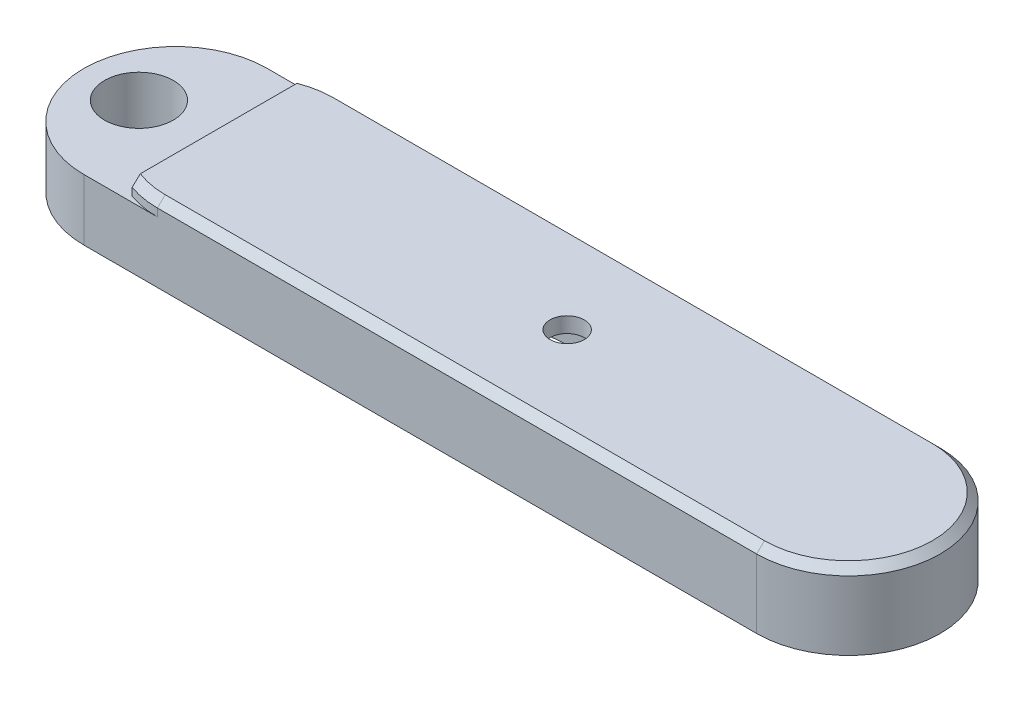
SolidWorks part; units mm, degrees
ref_plane "Front Plane" through (0, 0, 0) normal (0, 0, 1) x (1, 0, 0)
ref_plane "Top Plane" through (0, 0, 0) normal (0, 1, 0) x (1, 0, 0)
ref_plane "Right Plane" through (0, 0, 0) normal (1, 0, 0) x (0, 0, -1)
ref_plane "Plane1" through (0, 14.27, 0) normal (0, 1, 0) x (1, 0, 0)
sketch "Sketch1" plane through (0, 14.27, 0) normal (0, 1, 0) x (1, 0, 0)
  line L0 (8.0333, 3.025) -> (20.0462, 3.9053)
  line L1 (20.0462, 7.8947) -> (8.0333, 8.775)
  line L2 (3.7667, 8.775) -> (-8.2462, 7.8947)
  line L3 (-8.2462, 3.9053) -> (3.7667, 3.025)
  arc A0 (3.7667, 3.025) -> (8.0333, 3.025) centre (5.9, 5.9) ccw
  arc A1 (20.0462, 3.9053) -> (20.0462, 7.8947) centre (19.9, 5.9) ccw
  arc A2 (8.0333, 8.775) -> (3.7667, 8.775) centre (5.9, 5.9) ccw
  arc A3 (-8.2462, 7.8947) -> (-8.2462, 3.9053) centre (-8.1, 5.9) ccw
extrude "Boss-Extrude1" add sketch "Sketch1" against normal blind 1.6
sketch "Sketch2" plane through (0, 12.67, 0) normal (0, -1, 0) x (1, 0, 0)
  circle A0 centre (5.9, -5.9) radius 3.58
extrude "Boss-Extrude2" add sketch "Sketch2" along normal blind 1.83
ref_plane "Plane2" [suppressed] through (0, 0, -5.9) normal (0, 0, 1) x (1, 0, 0)
sketch "Sketch3" [suppressed] plane through (0, 0, -5.9) normal (0, 0, 1) x (1, 0, 0)
  line L0 (8.325, 14.27) -> (5.9, 14.27)
  line L1 (5.9, 14.27) -> (5.9, 10.84)
  line L2 (5.9, 10.84) -> (8.2, 10.84)
  line L3 (8.2, 10.84) -> (8.2, 13.2)
  line L4 (8.2, 13.2) -> (6.75, 13.2)
  line L5 (6.75, 13.2) -> (6.75, 13.65)
  line L6 (6.75, 13.65) -> (8.325, 13.65)
  line L7 (8.325, 13.65) -> (8.325, 14.27)
  line L8 (5.9, 14.27) -> (5.9, 10.84) construction
revolve "Cut-Revolve1" [suppressed] cut sketch "Sketch3" angle 360 about L8 reverse direction yes
hole_wizard "Ø1.0 (1) Diameter Hole1" positions "Sketch5" profile "Sketch4" hole size "Ø1.0" standard "ANSI Metric"
sketch "Sketch5" plane through (0, 12.67, 0) normal (0, -1, 0) x (-1, 0, 0)
  point P0 (2.7, 5.9)
  point P1 (6.7, 5.9)
  point P2 (8.7, 5.9)
  point P3 (4.7, 5.9)
  point P4 (0.7, 5.9)
  point P5 (-10.5, 5.9)
  point P6 (-14.5, 5.9)
  point P7 (-18.5, 5.9)
  point P8 (-20.5, 5.9)
  point P9 (-16.5, 5.9)
  point P10 (-12.5, 5.9)
  point P11 (-1.3, 5.9)
sketch "Sketch4" plane through (-2.7, 12.67, -5.9) normal (1, 0, 0) x (0, 0, -1)
  line L0 (0, 0) -> (0, 1.6)
  line L1 (0, 1.6) -> (0.5, 1.6)
  line L2 (0.5, 1.6) -> (0.5, 0)
  line L5 (0.5, 0) -> (0, 0)
  line L11 (0, -6.35) -> (0, 107.95) construction
  dimension "Thru Hole Dia." = 1
  dimension "Thru Hole Depth" = 1.6
sketch "Sketch6" plane through (0, 14.27, 0) normal (0, 1, 0) x (1, 0, 0)
  line L15 (3.7302, 9.2737) -> (-8.2827, 8.3933)
  line L16 (-8.2827, 3.4067) -> (3.7302, 2.5263)
  line L17 (3.5905, 9.2634) -> (-8.2827, 8.3933)
  line L18 (-8.2827, 3.4067) -> (3.5905, 2.5366)
  line L21 (-14.425, 1.1375) -> (20.5, 1.1375)
  line L22 (20.5, 10.6625) -> (-14.425, 10.6625)
  line L23 (20.0827, 8.3933) -> (8.0698, 9.2737)
  line L24 (8.0698, 2.5263) -> (20.0827, 3.4067)
  line L25 (20.0827, 8.3933) -> (8.2095, 9.2634)
  line L26 (8.2095, 2.5366) -> (20.0827, 3.4067)
  arc A8 (-8.2827, 8.3933) -> (-8.2827, 3.4067) centre (-8.1, 5.9) ccw
  arc A9 (-8.2827, 8.3933) -> (-8.2827, 3.4067) centre (-8.1, 5.9) ccw
  arc A12 (20.0827, 3.4067) -> (20.0827, 8.3933) centre (19.9, 5.9) ccw
  arc A13 (20.0827, 3.4067) -> (20.0827, 8.3933) centre (19.9, 5.9) ccw
  arc A14 (8.2095, 9.2634) -> (3.5905, 9.2634) centre (5.9, 5.9) ccw
  circle A15 centre (5.9, 5.9) radius 4.08
  arc A16 (3.5905, 2.5366) -> (8.2095, 2.5366) centre (5.9, 5.9) ccw
  arc A17 (20.5, 1.1375) -> (20.5, 10.6625) centre (20.5, 5.9) ccw
  arc A18 (-14.425, 10.6625) -> (-14.425, 1.1375) centre (-14.425, 5.9) ccw
  dimension "D4" = 34.925
  dimension "D1" = 0.5
  dimension "D2" = 0.5
  dimension "D3" = 0.5
extrude "Boss-Extrude3" add sketch "Sketch6" against normal blind 3.175 separate body
sketch "Sketch7" plane through (0, 14.27, 0) normal (0, 1, 0) x (1, 0, 0)
  line L4 (8.0333, 3.025) -> (20.0462, 3.9053)
  line L5 (20.0462, 7.8947) -> (8.0333, 8.775)
  line L6 (3.7667, 8.775) -> (-8.2462, 7.8947)
  line L7 (-8.2462, 3.9053) -> (3.7667, 3.025)
  line L8 (8.0333, 3.025) -> (20.0462, 3.9053)
  line L9 (20.0462, 7.8947) -> (8.0333, 8.775)
  line L10 (3.7667, 8.775) -> (-8.2462, 7.8947)
  line L11 (-8.2462, 3.9053) -> (3.7667, 3.025)
  arc A4 (3.7667, 3.025) -> (8.0333, 3.025) centre (5.9, 5.9) ccw
  arc A5 (20.0462, 3.9053) -> (20.0462, 7.8947) centre (19.9, 5.9) ccw
  arc A6 (8.0333, 8.775) -> (3.7667, 8.775) centre (5.9, 5.9) ccw
  arc A7 (-8.2462, 7.8947) -> (-8.2462, 3.9053) centre (-8.1, 5.9) ccw
  arc A8 (3.7667, 3.025) -> (8.0333, 3.025) centre (5.9, 5.9) ccw
  arc A9 (20.0462, 3.9053) -> (20.0462, 7.8947) centre (19.9, 5.9) ccw
  arc A10 (8.0333, 8.775) -> (3.7667, 8.775) centre (5.9, 5.9) ccw
  arc A11 (-8.2462, 7.8947) -> (-8.2462, 3.9053) centre (-8.1, 5.9) ccw
  dimension "D1" = 0
extrude "Cut-Extrude1" cut sketch "Sketch7" against normal blind 3.175
sketch "Sketch8" plane through (0, 11.095, 0) normal (0, 1, 0) x (1, 0, 0)
  circle A1 centre (5.9, 5.9) radius 3.58
  circle A2 centre (5.9, 5.9) radius 3.58
  dimension "D1" = 0
extrude "Cut-Extrude2" cut sketch "Sketch8" against normal blind 3.175
sketch "Sketch9" plane through (0, 14.27, 0) normal (0, 1, 0) x (1, 0, 0)
  line L0 (20.5, 10.6625) -> (20.5, 1.1375) construction
  line L1 (20.5, 5.9) -> (-10.6, 5.9) construction
  line L2 (20.5, 1.1375) -> (-10.6, 1.1375)
  line L3 (20.5, 10.6625) -> (-10.6, 10.6625)
  line L4 (-12.1875, 10.3901) -> (-12.1875, 1.4099)
  arc A0 (-8.2827, 8.3933) -> (-8.2827, 3.4067) centre (-8.1, 5.9) ccw construction
  arc A1 (20.5, 1.1375) -> (20.5, 10.6625) centre (20.5, 5.9) ccw
  arc A2 (-10.6, 10.6625) -> (-12.1875, 10.3901) centre (-10.6, 5.9) ccw
  arc A3 (-12.1875, 1.4099) -> (-10.6, 1.1375) centre (-10.6, 5.9) ccw
  point P9 (4.95, 5.9)
  dimension "D1" = 1.5875
extrude "Boss-Extrude4" add sketch "Sketch9" along normal blind 0.8
sketch "Sketch10" plane through (0, 14.27, 0) normal (0, 1, 0) x (1, 0, 0)
  circle A0 centre (5.9, 5.9) radius 0.889
extrude "Cut-Extrude3" cut sketch "Sketch10" against normal through all both and the other way through all
chamfer "Chamfer2" distance 0.4 angle 45 5 edges at (4.95, 15.07, -10.6625) (25.2625, 15.07, -5.9) (4.95, 15.07, -1.1375) (-11.4053, 15.07, -10.5939) (-11.4053, 15.07, -1.2061)
hole_wizard "9/64 (0.14063) Diameter Hole1" positions "Sketch12" profile "Sketch11" hole size "9/64" standard "ANSI Inch" end condition through all
sketch "Sketch12" plane through (0, 14.27, 0) normal (0, 1, 0) x (1, 0, 0)
  line L0 (-19.1875, 5.9) -> (5.9, 5.9) construction
  arc A0 (-14.425, 10.6625) -> (-14.425, 1.1375) centre (-14.425, 5.9) ccw construction
  point P8 (-16.325, 5.9)
  dimension "D1" = 22.225
sketch "Sketch11" plane through (-16.325, 14.27, -5.9) normal (1, 0, 0) x (0, 0, 1)
  line L0 (0, 0) -> (0, 3.175)
  line L1 (0, 3.175) -> (1.786, 3.175)
  line L2 (1.786, 3.175) -> (1.786, 0)
  line L5 (1.786, 0) -> (0, 0)
  line L11 (0, -6.35) -> (0, 107.95) construction
  dimension "Thru Hole Dia." = 3.572
  dimension "Thru Hole Depth" = 3.175
